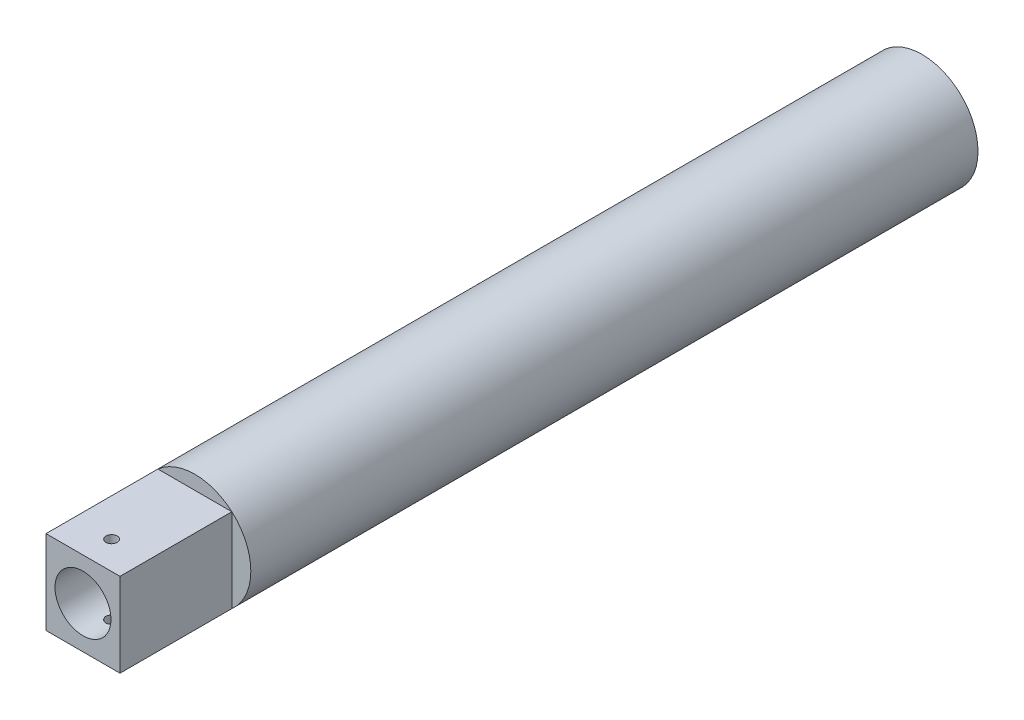
SolidWorks part; units mm, degrees
material "1060 Alloy"
ref_plane "Front Plane" through (0, 0, 0) normal (0, 0, 1) x (1, 0, 0)
ref_plane "Top Plane" through (0, 0, 0) normal (0, 1, 0) x (1, 0, 0)
ref_plane "Right Plane" through (0, 0, 0) normal (1, 0, 0) x (0, 0, -1)
sketch "Sketch1" plane through (0, 0, 0) normal (0, 0, 1) x (1, 0, 0)
  circle A0 centre (0, 0) radius 10
  dimension "D1" = 20
extrude "Boss-Extrude1" add sketch "Sketch1" along normal blind 150
sketch "Sketch2" plane through (0, 0, 150) normal (0, 0, 1) x (1, 0, 0)
  line L1 (-6.6144, 7.5) -> (6.6144, 7.5)
  line L2 (-6.6144, 7.5) -> (-6.6144, -7.5)
  line L3 (-6.6144, -7.5) -> (6.6144, -7.5)
  line L4 (6.6144, 7.5) -> (6.6144, -7.5)
  circle A0 centre (0, 0) radius 10 construction
  circle A1 centre (0, 0) radius 10
  point P0 (0, 0)
  circle M3 centre (0, 0) radius 10
  dimension "D1" = 15
extrude "Cut-Extrude1" cut sketch "Sketch2" against normal blind 20 contours L1 M3 | L4 M3 | L3 M3 | L2 M3 region at (0, 8.5116, 150) region at (-7.9904, 0, 150) region at (7.9904, 0, 150) region at (0, -8.5116, 150)
sketch "Sketch3" plane through (0, 7.5, 0) normal (0, 1, 0) x (1, 0, 0)
  line L0 (6.6144, -130) -> (6.6144, -150) construction
  line L1 (-6.6144, -150) -> (6.6144, -150) construction
  circle A0 centre (0.1144, -145) radius 2
  circle A1 centre (0.1144, -145) radius 1
  dimension "D3" = 4
  dimension "D4" = 2
  dimension "D1" = 6.5
  dimension "D2" = 5
extrude "Cut-Extrude2" [suppressed] cut sketch "Sketch3" against normal blind 2.5
extrude "Cut-Extrude4" cut sketch "Sketch3<3>" along direction (0, -1, 0) on the side against the normal through all contours A1 region at (0.1144, 7.5, 145)
sketch "Sketch3<3>" plane through (0, 7.5, 0) normal (0, 1, 0) x (1, 0, 0) same geometry as "Sketch3"
sketch "Sketch7" plane through (0, 0, 0) normal (0, 0, -1) x (-1, 0, 0)
  line L0 (-7.5, 0) -> (7.5, 0) construction
  line L1 (0, 10) -> (0, -10) construction
  circle A0 centre (7.5, 0) radius 1
  circle A1 centre (-7.5, 0) radius 1
  circle A2 centre (0, 0) radius 10 construction
  point P9 (0, 0)
  dimension "D1" = 2
  dimension "D2" = 2
  dimension "D3" = 15
extrude "Cut-Extrude5" cut sketch "Sketch7" against normal blind 10
sketch "Sketch8" plane through (0, 0, 0) normal (0, 0, -1) x (-1, 0, 0)
  circle A0 centre (0, 0) radius 5
  dimension "D1" = 10
extrude "Cut-Extrude6" cut sketch "Sketch8" against normal through all
